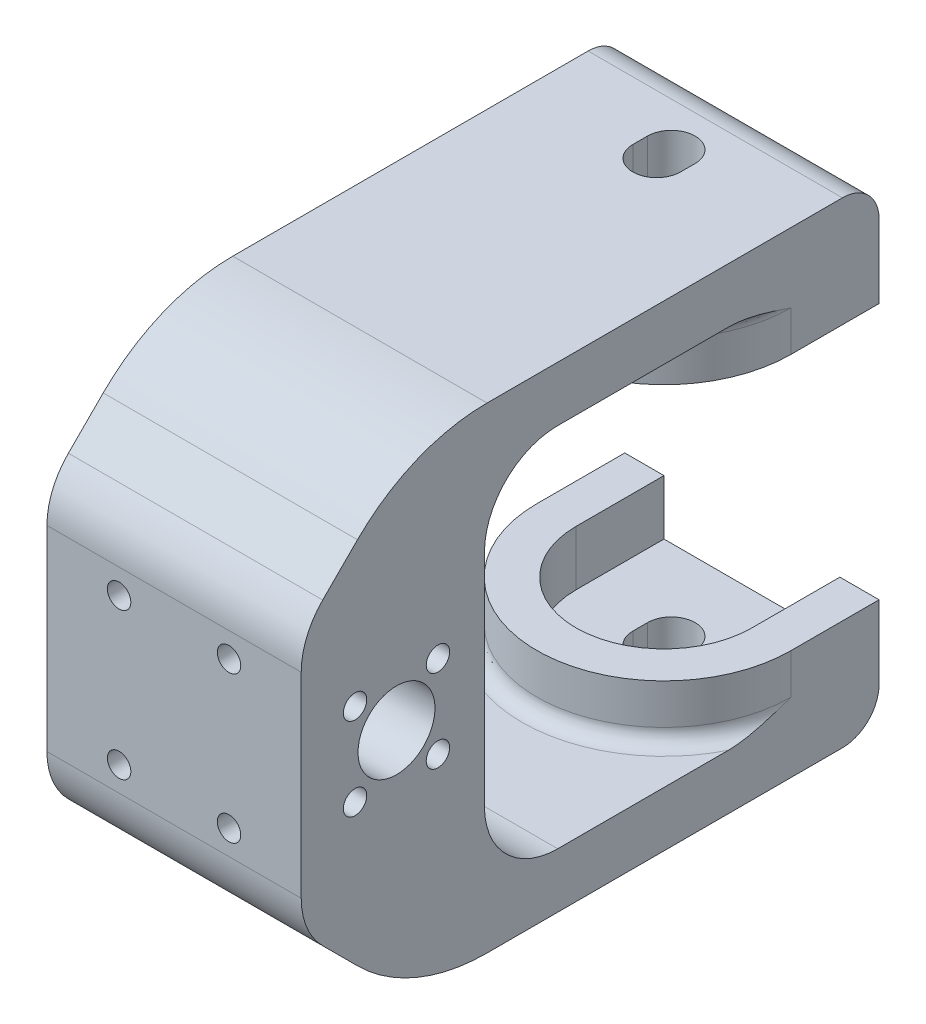
SolidWorks part; units mm, degrees
material "ABS"
ref_plane "Front Plane" through (0, 0, 0) normal (0, 0, 1) x (1, 0, 0)
ref_plane "Top Plane" through (0, 0, 0) normal (0, 1, 0) x (1, 0, 0)
ref_plane "Right Plane" through (0, 0, 0) normal (1, 0, 0) x (0, 0, -1)
sketch "Sketch1" plane through (0, 0, 0) normal (0, 0, 1) x (1, 0, 0)
  line L0 (0, 0) -> (0, -10) construction
  line L1 (17.35, 13.5) -> (-17.35, 13.5)
  line L2 (17.35, 13.5) -> (17.35, -13.5)
  line L3 (17.35, -13.5) -> (-17.35, -13.5)
  line L4 (-17.35, 13.5) -> (-17.35, -13.5)
  line L5 (17.35, 13.5) -> (-17.35, -13.5) construction
  line L6 (17.35, -13.5) -> (-17.35, 13.5) construction
  line L7 (0, -10) -> (-7.5, -10) construction
  line L8 (55, 0) -> (-55, 0) construction
  circle A0 centre (-7.5, -10) radius 1.6
  circle A1 centre (7.5, -10) radius 1.6
  circle A2 centre (7.5, 10) radius 1.6
  circle A3 centre (-7.5, 10) radius 1.6
  point P0 (0, 0)
  dimension "D5" = 3.2
  dimension "D1" = 34.7
  dimension "D2" = 27
  dimension "D3" = 10
  dimension "D4" = 7.5
extrude "Boss-Extrude1" add sketch "Sketch1" along normal blind 25
sketch "Sketch2" [suppressed] plane through (0, -13.5, 0) normal (0, -1, 0) x (1, 0, 0)
  line L0 (0, 0) -> (0, 12) construction
  line L1 (0, 12) -> (-5.6569, 17.6569) construction
  line L2 (0, 12) -> (-11.1, 12) construction
  circle A0 centre (0, 12) radius 5.25
  circle A1 centre (0, 12) radius 11.1
  circle A2 centre (-5.6569, 17.6569) radius 1.6
  circle A3 centre (0, 12) radius 11.1
  circle A4 centre (5.6569, 17.6569) radius 1.6
  circle A5 centre (0, 12) radius 11.1
  circle A6 centre (5.6569, 6.3431) radius 1.6
  circle A7 centre (0, 12) radius 11.1
  circle A8 centre (-5.6569, 6.3431) radius 1.6
  point P20 (0, 12)
  dimension "D2" = 10.5
  dimension "D3" = 22.2
  dimension "D5" = 3.2
  dimension "D1" = 12
  dimension "D4" = 8
  dimension "D6" = 45
  dimension "D7" = 4
sketch "Sketch4" plane through (-17.35, 0, 0) normal (-1, 0, 0) x (0, 0, 1)
  line L0 (0, 0) -> (12, 0) construction
  line L1 (12, 0) -> (6.3431, 5.6569) construction
  line L2 (6.3431, 5.6569) -> (6.3431, -5.6569) construction
  line L3 (6.3431, -5.6569) -> (17.6569, -5.6569) construction
  circle A0 centre (12, 0) radius 11.25
  circle A1 centre (12, 0) radius 5.25
  circle A2 centre (6.3431, 5.6569) radius 1.6
  circle A3 centre (17.6569, 5.6569) radius 1.6
  circle A4 centre (17.6569, -5.6569) radius 1.6
  circle A5 centre (6.3431, -5.6569) radius 1.6
  point P17 (12, 0)
  dimension "D2" = 22.5
  dimension "D3" = 10.5
  dimension "D6" = 3.2
  dimension "D1" = 12
  dimension "D4" = 45
  dimension "D5" = 8
  dimension "D8" = 11.3137
  dimension "D7" = 4
extrude "Base Extrude" cut sketch "Sketch4" against normal through all contours A2 | A3 | A4 | A5 | A1 region at (-17.35, 0, 12) region at (-17.35, 5.6569, 6.3431) region at (-17.35, 5.6569, 17.6569) region at (-17.35, -5.6569, 17.6569) region at (-17.35, -5.6569, 6.3431)
extrude "Cut-Extrude3" cut sketch "Sketch4<3>" against normal blind 5
sketch "Sketch4<3>" plane through (-17.35, 0, 0) normal (-1, 0, 0) x (0, 0, 1) same geometry as "Sketch4"
sketch "Sketch10" plane through (17.35, 0, 0) normal (1, 0, 0) x (0, 0, -1)
  line L0 (0, 13.5) -> (0, 25)
  line L1 (53.85, 25) -> (29.85, 25) construction
  line L2 (53.85, 25) -> (0, 25)
  line L3 (-25, 13.5) -> (-25, 32.5)
  line L4 (-25, 32.5) -> (53.85, 32.5)
  line L5 (53.85, 32.5) -> (53.85, 25)
  line L6 (-25, 13.5) -> (0, 13.5)
  line L8 (19.085, 0) -> (-19.085, 0) construction
  line L9 (-25, -13.5) -> (-25, -32.5)
  line L10 (-25, -32.5) -> (53.85, -32.5)
  line L11 (53.85, -32.5) -> (53.85, -25)
  line L12 (53.85, -25) -> (0, -25)
  line L13 (0, -13.5) -> (0, -25)
  line L14 (-25, -13.5) -> (0, -13.5)
  dimension "D1" = 7.5
extrude "Boss-Extrude5" add sketch "Sketch10" against normal up to vertex (34.7 mm away) up to point (-17.35, 13.5, 25)
chamfer "Chamfer3" distance 12.5 distance2 15 1 edges at (0, 32.5, 25) first distance on face at (0, 0, 25)
fillet "Fillet1" radius 10 1 edges at (0, 25, 0)
fillet "Fillet3" radius 20 1 edges at (0, 32.5, 10)
fillet "Fillet4" radius 7.5 1 edges at (0, 20, 25)
sketch "Sketch11" plane through (0, 25, 0) normal (0, -1, 0) x (1, 0, 0)
  line L0 (-12, -53.85) -> (-17.35, -53.85)
  line L1 (0, -41.85) -> (0, -53.85) construction
  line L2 (-17.35, -53.85) -> (17.35, -53.85) construction
  line L3 (12, -41.85) -> (12, -53.85)
  line L4 (-12, -41.85) -> (-12, -53.85)
  line L5 (17.35, -41.85) -> (17.35, -53.85)
  line L6 (-17.35, -53.85) -> (-17.35, -41.85)
  line L7 (12, -53.85) -> (17.35, -53.85)
  arc A0 (12, -41.85) -> (-12, -41.85) centre (0, -41.85) ccw
  arc A3 (17.35, -41.85) -> (-17.35, -41.85) centre (0, -41.85) ccw
  dimension "D1" = 24
extrude "Boss-Extrude6" add sketch "Sketch11" along normal blind 7.5
fillet "Fillet5" radius 2 1 edges at (0, 25, -24.5)
sketch "Sketch13" plane through (0, 25, 0) normal (0, -1, 0) x (1, 0, 0)
  line L0 (-12, -41.85) -> (12, -41.85) construction
  line L1 (0, -29.85) -> (0, -41.85) construction
  arc A0 (12, -41.85) -> (-12, -41.85) centre (0, -41.85) ccw construction
  circle A1 centre (0, -41.85) radius 3.25
  dimension "D1" = 6.5
extrude "Cut-Extrude5" cut sketch "Sketch13" against normal blind 18.5
mirror "Mirror12" about plane through (0, 0, 0) normal (0, 1, 0) of bodies 112
chamfer "Chamfer4" distance 15 distance2 15 2 edges at (0, -32.5, 25) (0, 32.5, 25)
fillet "Fillet11" radius 10 2 edges at (0, -17.5, 25) (0, 17.5, 25)
fillet "Fillet12" radius 25 2 edges at (0, 32.5, 10) (0, -32.5, 10)
fillet "Fillet13" radius 5 2 edges at (0, -32.5, -53.85) (0, 32.5, -53.85)
sketch "Sketch14" plane through (0, 0, 0) normal (0, 1, 0) x (1, 0, 0)
  line L0 (0, 40.85) -> (0, 42.85) construction
  line L1 (-3.25, 40.85) -> (-3.25, 42.85)
  line L2 (3.25, 40.85) -> (3.25, 42.85)
  line L3 (12, 53.85) -> (-12, 53.85)
  line L4 (-12, 53.85) -> (-12, 41.85)
  line L5 (12, 41.85) -> (12, 53.85)
  line L6 (12, 53.85) -> (-12, 53.85) construction
  line L7 (-12, 53.85) -> (-12, 41.85) construction
  line L8 (12, 41.85) -> (12, 53.85) construction
  arc A0 (-3.25, 40.85) -> (3.25, 40.85) centre (0, 40.85) ccw
  arc A1 (-12, 41.85) -> (12, 41.85) centre (0, 41.85) ccw
  arc A2 (-12, 41.85) -> (12, 41.85) centre (0, 41.85) ccw construction
  arc A3 (3.25, 42.85) -> (-3.25, 42.85) centre (0, 42.85) ccw
  point P7 (0, 41.85)
  dimension "D3" = 3.25
  dimension "D2" = 2
  dimension "D1" = 0
extrude "Cut-Extrude6" cut sketch "Sketch14" against normal through all both and the other way through all
